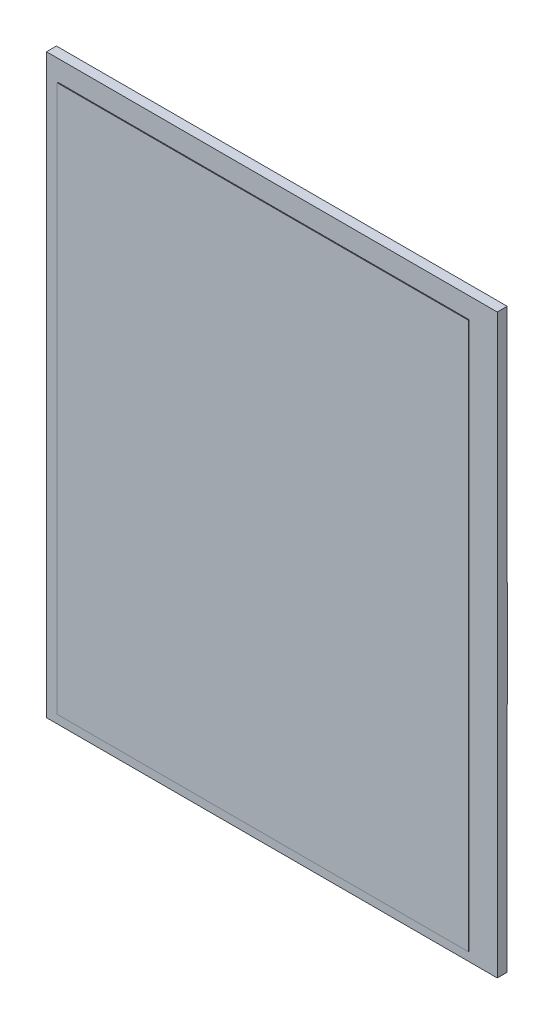
SolidWorks part; units mm, degrees
ref_plane "Front Plane" through (0, 0, 0) normal (0, 0, 1) x (1, 0, 0)
ref_plane "Top Plane" through (0, 0, 0) normal (0, 1, 0) x (1, 0, 0)
ref_plane "Right Plane" through (0, 0, 0) normal (1, 0, 0) x (0, 0, -1)
sketch "Sketch1" plane through (0, 0, 0) normal (0, 0, 1) x (1, 0, 0)
  line L0 (-68, -87) -> (68, -87)
  line L1 (-68, -87) -> (-68, 87)
  line L2 (68, -87) -> (68, 87)
  line L3 (-68, 87) -> (68, 87)
  line L4 (-68, -87) -> (68, 87) construction
  line L5 (68, -87) -> (-68, 87) construction
  point P1 (0, 0)
  dimension "D1" = 136
  dimension "D2" = 174
extrude "Boss-Extrude1" add sketch "Sketch1" along normal blind 3
sketch "Sketch2" plane through (0, 0, 3) normal (0, 0, 1) x (1, 0, 0)
  line L0 (-64.5, -84.25) -> (59.5, -84.25)
  line L1 (-64.5, -84.25) -> (-64.5, 80.75)
  line L2 (59.5, -84.25) -> (59.5, 80.75)
  line L3 (-64.5, 80.75) -> (59.5, 80.75)
  line L4 (-64.5, -84.25) -> (59.5, 80.75) construction
  line L5 (59.5, -84.25) -> (-64.5, 80.75) construction
  line L6 (68, -87) -> (68, 87) construction
  line L7 (68, 87) -> (-68, 87) construction
  line L8 (-68, -87) -> (68, -87) construction
  line L9 (-68, 87) -> (-68, -87) construction
  point P1 (-2.5, -1.75)
  dimension "D1" = 124
  dimension "D2" = 165
  dimension "D3" = 8.5
  dimension "D4" = 6.25
  dimension "D5" = 2.75
  dimension "D6" = 3.5
extrude "Boss-Extrude2" add sketch "Sketch2" along normal blind 0.25
sketch "Sketch3" plane through (0, 0, 0) normal (0, 0, -1) x (-1, 0, 0)
  line L0 (-68, 14.75) -> (-68, -17)
  line L1 (-68, 14.75) -> (-48, 14.75)
  line L2 (-68, -17) -> (-48, -17)
  line L3 (-48, 14.75) -> (-48, -17)
  line L4 (-68, -87) -> (-68, 87) construction
  line L5 (-68, 87) -> (68, 87) construction
  dimension "D1" = 31.75
  dimension "D2" = 72.25
  dimension "D3" = 20
extrude "Boss-Extrude3" add sketch "Sketch3" along normal blind 0.1
sketch "Sketch4" plane through (0, 0, 3.25) normal (0, 0, 1) x (1, 0, 0)
  line L0 (-64.5, -1.75) -> (59.5, -1.75)
  line L1 (-64.5, 80.75) -> (-64.5, -84.25) construction
  line L2 (59.5, -84.25) -> (59.5, 80.75) construction
  point P1 (-2.5, -1.75)
